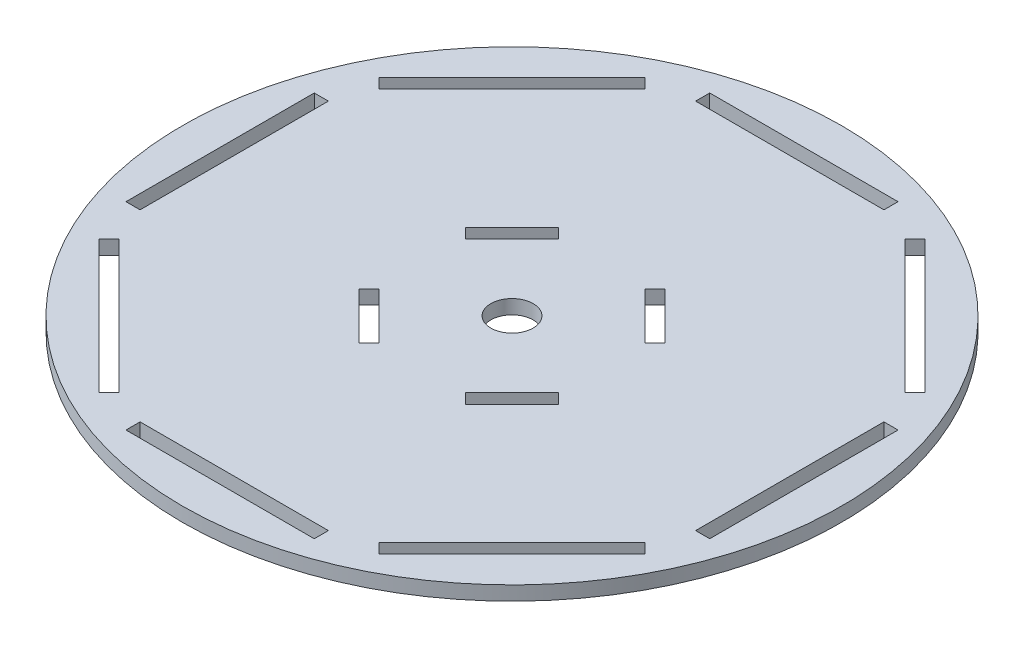
SolidWorks part; units mm, degrees
ref_plane "Alzado" through (0, 0, 0) normal (0, 0, 1) x (1, 0, 0)
ref_plane "Planta" through (0, 0, 0) normal (0, 1, 0) x (1, 0, 0)
ref_plane "Vista lateral" through (0, 0, 0) normal (1, 0, 0) x (0, 0, -1)
sketch "Croquis1" plane through (0, 0, 0) normal (0, 1, 0) x (1, 0, 0)
  line L10 (0, 0) -> (-14.1421, 14.1421) construction
  line L11 (-14.1421, 14.1421) -> (-9.1924, 19.0919)
  line L12 (-9.1924, 19.0919) -> (-11.3137, 21.2132)
  line L23 (-11.3137, 21.2132) -> (-21.2132, 11.3137)
  line L24 (-14.1421, 14.1421) -> (-19.0919, 9.1924)
  line L25 (-19.0919, 9.1924) -> (-21.2132, 11.3137)
  line L26 (21.2132, 11.3137) -> (11.3137, 21.2132)
  line L27 (14.1421, 14.1421) -> (19.0919, 9.1924)
  line L28 (14.1421, 14.1421) -> (9.1924, 19.0919)
  line L29 (9.1924, 19.0919) -> (11.3137, 21.2132)
  line L30 (19.0919, 9.1924) -> (21.2132, 11.3137)
  line L31 (11.3137, -21.2132) -> (21.2132, -11.3137)
  line L32 (14.1421, -14.1421) -> (9.1924, -19.0919)
  line L33 (14.1421, -14.1421) -> (19.0919, -9.1924)
  line L34 (19.0919, -9.1924) -> (21.2132, -11.3137)
  line L35 (9.1924, -19.0919) -> (11.3137, -21.2132)
  line L36 (-21.2132, -11.3137) -> (-11.3137, -21.2132)
  line L37 (-14.1421, -14.1421) -> (-19.0919, -9.1924)
  line L38 (-14.1421, -14.1421) -> (-9.1924, -19.0919)
  line L39 (-9.1924, -19.0919) -> (-11.3137, -21.2132)
  line L40 (-19.0919, -9.1924) -> (-21.2132, -11.3137)
  line L41 (0, 0) -> (0, 62) construction
  line L42 (0, 62) -> (20, 62)
  line L43 (20, 62) -> (20, 59)
  line L44 (20, 59) -> (-20, 59)
  line L45 (-20, 59) -> (-20, 62)
  line L46 (-20, 62) -> (0, 62)
  line L47 (55.8614, 27.5772) -> (27.5772, 55.8614)
  line L48 (27.5772, 55.8614) -> (29.6985, 57.9828)
  line L49 (29.6985, 57.9828) -> (43.8406, 43.8406)
  line L50 (43.8406, 43.8406) -> (57.9828, 29.6985)
  line L51 (57.9828, 29.6985) -> (55.8614, 27.5772)
  line L52 (59, -20) -> (59, 20)
  line L53 (59, 20) -> (62, 20)
  line L54 (62, 20) -> (62, 0)
  line L55 (62, 0) -> (62, -20)
  line L56 (62, -20) -> (59, -20)
  line L57 (27.5772, -55.8614) -> (55.8614, -27.5772)
  line L58 (55.8614, -27.5772) -> (57.9828, -29.6985)
  line L59 (57.9828, -29.6985) -> (43.8406, -43.8406)
  line L60 (43.8406, -43.8406) -> (29.6985, -57.9828)
  line L61 (29.6985, -57.9828) -> (27.5772, -55.8614)
  line L62 (-20, -59) -> (20, -59)
  line L63 (20, -59) -> (20, -62)
  line L64 (20, -62) -> (0, -62)
  line L65 (0, -62) -> (-20, -62)
  line L66 (-20, -62) -> (-20, -59)
  line L67 (-55.8614, -27.5772) -> (-27.5772, -55.8614)
  line L68 (-27.5772, -55.8614) -> (-29.6985, -57.9828)
  line L69 (-29.6985, -57.9828) -> (-43.8406, -43.8406)
  line L70 (-43.8406, -43.8406) -> (-57.9828, -29.6985)
  line L71 (-57.9828, -29.6985) -> (-55.8614, -27.5772)
  line L72 (-59, 20) -> (-59, -20)
  line L73 (-59, -20) -> (-62, -20)
  line L74 (-62, -20) -> (-62, 0)
  line L75 (-62, 0) -> (-62, 20)
  line L76 (-62, 20) -> (-59, 20)
  line L77 (-27.5772, 55.8614) -> (-55.8614, 27.5772)
  line L78 (-55.8614, 27.5772) -> (-57.9828, 29.6985)
  line L79 (-57.9828, 29.6985) -> (-43.8406, 43.8406)
  line L80 (-43.8406, 43.8406) -> (-29.6985, 57.9828)
  line L81 (-29.6985, 57.9828) -> (-27.5772, 55.8614)
  circle A0 centre (0, 0) radius 4.5
  circle A2 centre (0, 0) radius 70
  point P47 (0, 0)
  point P88 (0, 0)
  dimension "D2" = 7
  dimension "D3" = 140
  dimension "D9" = 7
  dimension "D10" = 3
  dimension "D15" = 20
  dimension "D16" = 3
  dimension "D17" = 40
  dimension "D13" = 4
  dimension "D18" = 8
extrude "Saliente-Extruir1" add sketch "Croquis1" along normal blind 3
